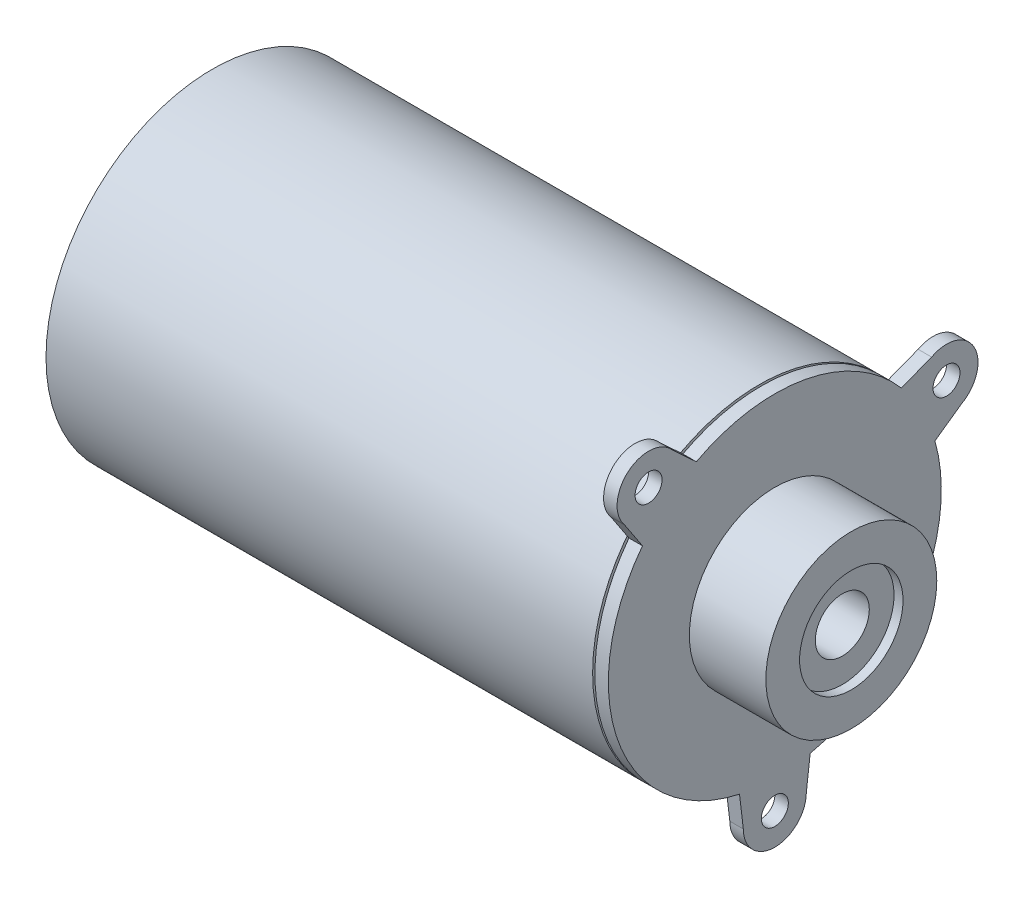
SolidWorks part; units mm, degrees
ref_plane "Front Plane" through (0, 0, 0) normal (0, 0, 1) x (1, 0, 0)
ref_plane "Top Plane" through (0, 0, 0) normal (0, 1, 0) x (1, 0, 0)
ref_plane "Right Plane" through (0, 0, 0) normal (1, 0, 0) x (0, 0, -1)
sketch "Sketch1" plane through (0, 0, 0) normal (1, 0, 0) x (0, 0, -1)
  line L0 (-16.6972, 14.2189) -> (-14.7104, 11.2185)
  line L1 (-3.9278, -18.0782) -> (-3.5, -21.65)
  line L2 (3.5, -21.65) -> (3.9278, -18.0782)
  line L3 (17.7948, 5.059) -> (20.7341, 7.1462)
  line L4 (17.4263, 13.3153) -> (14.0613, 12.0221)
  line L5 (-8.7223, 16.3148) -> (-11.3664, 18.7557)
  circle A0 centre (0, 0) radius 17.5
  circle A1 centre (0, 0) radius 18.5
  arc A2 (-14.7104, 11.2185) -> (-3.9278, -18.0782) centre (0, 0) ccw
  arc A3 (-3.5, -21.65) -> (3.5, -21.65) centre (0, -21.65) ccw
  arc A4 (3.9278, -18.0782) -> (17.7948, 5.059) centre (0, 0) ccw
  arc A5 (20.7341, 7.1462) -> (17.4263, 13.3153) centre (19.0802, 10.2307) ccw
  arc A6 (14.0613, 12.0221) -> (-8.7223, 16.3148) centre (0, 0) ccw
  arc A7 (-11.3664, 18.7557) -> (-16.6972, 14.2189) centre (-14.0318, 16.4873) ccw
  circle A8 centre (-14.0318, 16.4873) radius 1.5
  circle A9 centre (19.0802, 10.2307) radius 1.5
  circle A10 centre (0, -21.65) radius 1.5
  dimension "D1" = 35
  dimension "D2" = 3
extrude "Boss-Extrude1" add sketch "Sketch1" along normal blind 1.5 contours A0 | L5 A7 L0 A1 A8 | A1 A0 | L3 A5 L4 A1 A9 | L1 A3 L2 A1 A10 region at (0, 19.058, 16.2197) region at (0, 13.69, 11.6511) region at (0, -18.6057, 0) region at (0, 12.5552, -15.7874) region at (0, 0, 0)
extrude "Boss-Extrude2" add sketch "Sketch1<4>" against normal blind 61.5 contours A0 | A1 A0 region at (0, 13.69, 11.6511) region at (0, 0, 0)
sketch "Sketch1<4>" plane through (0, 0, 0) normal (1, 0, 0) x (0, 0, -1) same geometry as "Sketch1"
extrude "Cut-Extrude1" cut sketch "Sketch1<5>" along normal blind 6 from surface contours A0 region at (0, 0, 0) starting at face at (-61.5, 0, -18.5)
sketch "Sketch1<5>" plane through (0, 0, 0) normal (1, 0, 0) x (0, 0, -1) same geometry as "Sketch1"
sketch "Sketch2" plane through (1.5, 0, 0) normal (1, 0, 0) x (0, 0, -1)
  circle A0 centre (0, 0) radius 5.75
  circle A1 centre (0, 0) radius 9.5
extrude "Boss-Extrude3" add sketch "Sketch2" along normal blind 8.5 contours A0 | A1 A0 region at (1.5, 0, 0) region at (1.5, 0, 9.2313)
sketch "Sketch3" plane through (10, 0, 0) normal (1, 0, 0) x (0, 0, -1)
  circle A0 centre (0, 0) radius 5.75
  dimension "D1" = 11.5
extrude "Cut-Extrude2" cut sketch "Sketch3" against normal blind 1
sketch "Sketch4" plane through (9, 0, 0) normal (1, 0, 0) x (0, 0, -1)
  circle A0 centre (0, 0) radius 3
  dimension "D1" = 6
extrude "Cut-Extrude3" cut sketch "Sketch4" against normal through all both and the other way through all
sketch "Sketch5" plane through (1.5, 0, 0) normal (1, 0, 0) x (0, 0, -1)
  circle A0 centre (0, 0) radius 17.5
  circle A1 centre (0, 0) radius 18.5
  dimension "D1" = 35
extrude "Cut-Extrude4" cut sketch "Sketch5" against normal blind 0.25 from surface starting at face at (0, -20.8446, 0)
sketch "Sketch6" plane through (-61.5, 0, 0) normal (-1, 0, 0) x (0, 0, 1)
  circle A1 centre (0, 0) radius 18.5
  circle A2 centre (0, 0) radius 18.5
  dimension "D1" = 0
extrude "Cut-Extrude5" cut sketch "Sketch6" against normal blind 0.5
